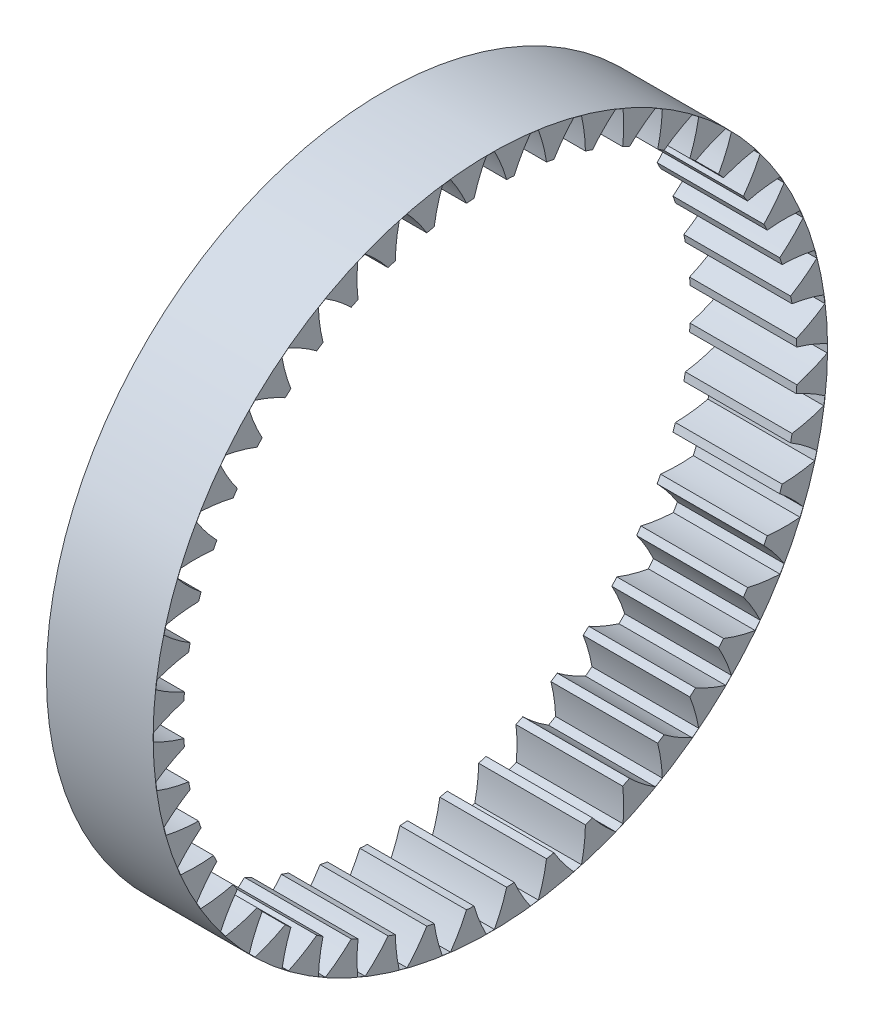
SolidWorks part; units mm, degrees
ref_plane "Plane1" through (0, 0, 0) normal (0, 0, 1) x (1, 0, 0)
ref_plane "Plane2" through (0, 0, 0) normal (0, 1, 0) x (1, 0, 0)
ref_plane "Plane3" through (0, 0, 0) normal (1, 0, 0) x (0, 0, -1)
sketch "HoldingSke" plane through (0, 0, 0) normal (0, 1, 0) x (1, 0, 0)
  line L0 (0, 0) -> (-0.6691, 0.7431)
  line L1 (-15, 0) -> (100, 0) construction
  line L2 (0, 0) -> (-2.1039, 2.3779)
  line L3 (0, 0) -> (-11.863, 4.5341)
  line L4 (0, 0) -> (5.7786, 6.4178)
  line L5 (0, 0) -> (-23.7986, -8.8762)
  line L6 (0, 0) -> (-10.5278, -7.1032)
  line L7 (-2.1039, 2.3779) -> (3.3635, 27.1825)
  line L8 (-76.2, 3.3779) -> (-54.61, 3.3779)
  line L9 (-71.009, 38.7566) -> (-53.1078, 45.2721)
  line L10 (-76.2, 71.12) -> (104.1128, 71.12)
  line L11 (0, 0) -> (-8, 0)
  line L12 (-76.2, 101.6) -> (-76.162, 101.6)
  line L13 (24.9733, 27.94) -> (52.9518, 28.4284)
  line L14 (24.9733, 27.94) -> (24.9743, 27.94)
  line L15 (24.9733, 27.94) -> (100.4006, 29.5858)
  circle A0 centre (0, 0) radius 12.5
  circle A1 centre (0, 0) radius 12.7
  circle A2 centre (0, 0) radius 12.7
  dimension "Num_teeth" = 48
  dimension "Pitch_radius" = 180.3128
  dimension "Width" = 8
sketch "BasProSke" plane through (0, 0, 0) normal (0, 1, 0) x (1, 0, 0)
  line L0 (-10, 0) -> (60, 0) construction
  line L1 (0, 23) -> (0, 25.2764)
  line L2 (0, 23) -> (8, 23)
  line L3 (8, 23) -> (8, 25.2764)
  line L4 (8, 25.2764) -> (0, 25.2764)
  dimension "Thickness" = 8
  dimension "Diameter" = 50.5528
revolve "Base-Revolve" add sketch "BasProSke" angle 360 about L0
sketch "TooCutSke" plane through (0, 0, 0) normal (1, 0, 0) x (0, 0, -1)
  line L3 (0.8803, 23.9839) -> (0.8803, 53.6633) construction
  line L4 (0, 0) -> (0, 59.563) construction
  line L5 (0, 0) -> (-4.4688, 68.1812) construction
  line L6 (-10.3155, 19.6648) -> (36.4343, 22.7289) construction
  circle A0 centre (0, 0) radius 24 construction
  circle A1 centre (0, 0) radius 25.251 construction
  circle A2 centre (0, 0) radius 20.2974 construction
  circle A3 centre (0, 0) radius 22.9746 construction
  arc A4 (1.2284, 22.9417) -> (0.3059, 25.2491) centre (-10.3155, 19.6648) ccw
  arc A5 (1.2284, 22.9417) -> (-1.2284, 22.9417) centre (0, 0) ccw
  arc A6 (0.3059, 25.2491) -> (-0.3059, 25.2491) centre (0, 0) ccw
  arc A7 (-0.3059, 25.2491) -> (-1.2284, 22.9417) centre (10.3155, 19.6648) ccw
extrude "ToothCut" cut sketch "TooCutSke" along normal through all
fillet "Breaks" [suppressed] radius 0.1
fillet "RootFillets" [suppressed] radius 0.251
pattern_circular "TeethCuts" count 48 every 7.5 about axis through (-10, 0, 0) along (1, 0, 0) of "RootFillets", "Breaks", "ToothCut"
equation "' \"Module@HoldingSke\" = 6.35"
equation "' \"Num_teeth@HoldingSke\" = 24"
equation "' \"Ap@HoldingSke\" =  14.5"
equation "' \"Ap@HoldingSke\" = 14.5"
equation "' \"Width@HoldingSke\" = 12"
equation "' \"Diameter@HoldingSke\" = 8 * 25.4"
equation "' \"Show_teeth@HoldingSke\" = 100"
equation "' \"Backlash@HoldingSke\" = 0.009 * 25.4"
equation "' \"Addendum_fac@HoldingSke\" = 1.0"
equation "' \"Dedendum_fac@HoldingSke\" = 1.25"
equation "' \"Dedendum_add@HoldingSke\" = 0.00005 * 25.4"
equation "' \"Clearance_fac@HoldingSke\" = 0.25"
equation "\"Pitch@HoldingSke\" = 1 / \"Module@HoldingSke\" "
equation "\"Overcut_dia@TooCutSke\" = (\"Num_teeth@HoldingSke\" - 2 * \"Addendum_fac@HoldingSke\") / \"Pitch@HoldingSke\" - 0.002 * 25.4"
equation "\"Pitch_dia@TooCutSke\" = \"Num_teeth@HoldingSke\" / \"Pitch@HoldingSke\""
equation "\"Base_dia@TooCutSke\" = \"Num_teeth@HoldingSke\" / \"Pitch@HoldingSke\" * cos((\"Ap@HoldingSke\"  * 3.14159265 / 180)) * 0.90"
equation "\"Root_dia@TooCutSke\" = \"Num_teeth@HoldingSke\"  / \"Pitch@HoldingSke\" + 2 *  \"Dedendum_fac@HoldingSke\"/ \"Pitch@HoldingSke\" + \"Dedendum_add@HoldingSke\" * 2"
equation "\"Half_ang@TooCutSke\" = 180 / \"Num_teeth@HoldingSke\""
equation "\"Half_CT@TooCutSke\" = \"Num_teeth@HoldingSke\" / \"Pitch@HoldingSke\" * sin((3.14159265 / 2 / \"Num_teeth@HoldingSke\")) / 2 + 10 * \"Backlash@HoldingSke\" / 4"
equation "\"Flank_rad@TooCutSke\" = \"Num_teeth@HoldingSke\" / \"Pitch@HoldingSke\" / 4"
equation "\"Radius@RootFillets\"= \"Clearance_fac@HoldingSke\" / \"Pitch@HoldingSke\" + \"Dedendum_add@HoldingSke\""
equation "\"Break_rad@Breaks\" = 0.02 / \"Pitch@HoldingSke\" * 5"
equation "\"Num_teeth@TeethCuts\" = int( \"Show_teeth@HoldingSke\" ) + 1"
equation "\"Num_teeth@TeethCuts\" = ((sgn( \"Num_teeth@TeethCuts\" - \"Num_teeth@HoldingSke\" )-1)*( \"Num_teeth@TeethCuts\" - \"Num_teeth@HoldingSke\" ))/-2+ \"Num_teeth@HoldingSke\""
equation "\"Num_teeth@TeethCuts\" = ((sgn( \"Num_teeth@TeethCuts\" - 2.0)+1)*( \"Num_teeth@TeethCuts\" - 2.0))/2 +2.0"
equation "\"Angle@TeethCuts\" = 360.0 / \"Num_teeth@HoldingSke\""
equation "\"Diameter@BasProSke\" = \"Num_teeth@HoldingSke\"  / \"Pitch@HoldingSke\" + 2 *  \"Dedendum_fac@HoldingSke\"/ \"Pitch@HoldingSke\" + \"Dedendum_add@HoldingSke\" * 2 + 0.002 * 25.4"
equation "\"Diameter@BasProSke\" = ((sgn( \"Diameter@BasProSke\"  - \"Diameter@HoldingSke\" )+1)*( \"Diameter@BasProSke\"  - \"Diameter@HoldingSke\" ))/2 + \"Diameter@HoldingSke\""
equation "\"Inside_diameter@BasProSke\" =  (\"Num_teeth@HoldingSke\" - 2 * \"Addendum_fac@HoldingSke\") / \"Pitch@HoldingSke\" "
equation "\"Thickness@BasProSke\"  = \"Width@HoldingSke\""
